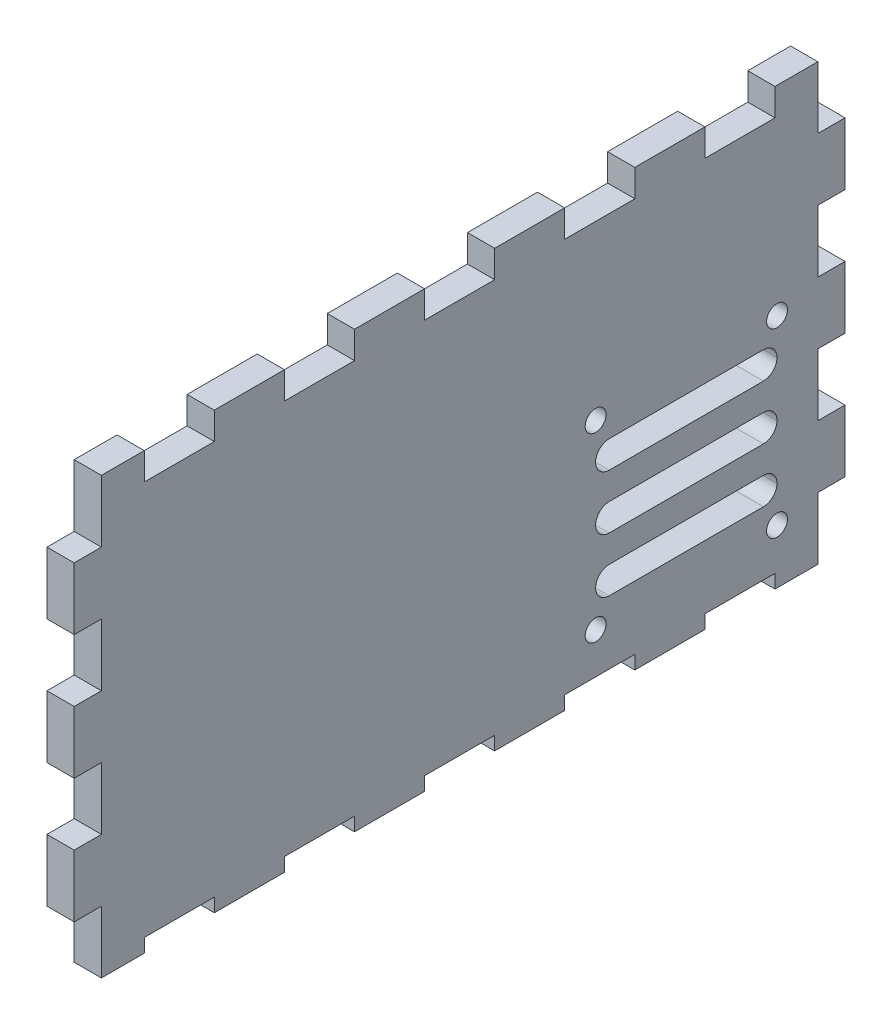
SolidWorks part; units mm, degrees
material "Balsa"
ref_plane "Front" through (0, 0, 0) normal (0, 0, 1) x (1, 0, 0)
ref_plane "Top" through (0, 0, 0) normal (0, 1, 0) x (1, 0, 0)
ref_plane "Right" through (0, 0, 0) normal (1, 0, 0) x (0, 0, -1)
sketch "Esboço1" plane through (0, 0, 0) normal (1, 0, 0) x (0, 0, -1)
  line L1 (85, -48) -> (-85, -48)
  line L2 (85, -48) -> (85, 48)
  line L3 (85, 48) -> (-85, 48)
  line L4 (-85, -48) -> (-85, 48)
  line L5 (85, -48) -> (-85, 48) construction
  line L6 (85, 48) -> (-85, -48) construction
  point P0 (0, 0)
  dimension "D1" = 170
  dimension "D2" = 96
extrude "Ressalto-extrusão1" add sketch "Esboço1" along normal blind 6
sketch "Esboço2" plane through (6, 0, 0) normal (1, 0, 0) x (0, 0, -1)
  line L0 (-7.7255, 42) -> (7.73, 42)
  line L1 (-38.6355, 42) -> (-23.18, 42)
  line L2 (-54.09, 48) -> (-69.5455, 48)
  line L3 (-23.18, 48) -> (-38.6355, 48)
  line L4 (-69.5455, 48) -> (-69.5455, 42)
  line L5 (-54.09, 48) -> (-54.09, 42)
  line L6 (23.1845, 42) -> (38.64, 42)
  line L7 (-38.6355, 48) -> (-38.6355, 42)
  line L8 (7.73, 48) -> (-7.7255, 48)
  line L9 (-23.18, 48) -> (-23.18, 42)
  line L10 (54.0945, 42) -> (69.55, 42)
  line L11 (-7.7255, 48) -> (-7.7255, 42)
  line L12 (38.64, 48) -> (23.1845, 48)
  line L13 (7.73, 48) -> (7.73, 42)
  line L14 (-54.09, -51) -> (-69.5455, -51)
  line L15 (23.1845, 48) -> (23.1845, 42)
  line L16 (-38.6355, -45) -> (-23.18, -45)
  line L17 (38.64, 48) -> (38.64, 42)
  line L18 (-7.7255, -45) -> (7.73, -45)
  line L19 (54.0945, 48) -> (54.0945, 42)
  line L20 (-23.18, -51) -> (-38.6355, -51)
  line L21 (69.55, 48) -> (69.55, 42)
  line L22 (23.1845, -45) -> (38.64, -45)
  line L23 (7.73, -51) -> (-7.7255, -51)
  line L24 (54.0945, -45) -> (69.55, -45)
  line L25 (-54.09, -45) -> (-54.09, -51)
  line L26 (38.64, -51) -> (23.1845, -51)
  line L27 (-38.6355, -45) -> (-38.6355, -51)
  line L29 (-23.18, -45) -> (-23.18, -51)
  line L31 (-7.7255, -45) -> (-7.7255, -51)
  line L33 (7.73, -45) -> (7.73, -51)
  line L35 (23.1845, -45) -> (23.1845, -51)
  line L37 (38.64, -45) -> (38.64, -51)
  line L39 (54.0945, -45) -> (54.0945, -51)
  line L41 (69.55, -45) -> (69.55, -51)
  line L47 (-69.5455, -45) -> (-69.5455, -51)
  line L48 (-69.5455, 42) -> (-54.09, 42)
  line L49 (69.55, 48) -> (54.0945, 48)
  line L50 (-69.5455, -45) -> (-54.09, -45)
  line L51 (69.55, -51) -> (54.0945, -51)
  line L53 (85.0045, 48) -> (85.0045, 42) [skipped]
  line L54 (85.0045, -45) -> (85.0045, -51) [skipped]
  dimension "D1" = 6
  dimension "D3" = 6
  dimension "D4" = 2
extrude "Corte-extrusão1" cut sketch "Esboço2" against normal up to next
sketch "Esboço3" plane through (6, 0, 0) normal (1, 0, 0) x (0, 0, -1)
  line L0 (79, -48) -> (85, -48)
  line L1 (-85, -48) -> (-79, -48)
  line L2 (-85, -48) -> (-85, -34.2857)
  line L3 (-85, -34.2857) -> (-79, -34.2857)
  line L4 (-79, -48) -> (-79, -34.2857)
  line L5 (79, -48) -> (79, -34.2857)
  line L6 (79, -34.2857) -> (85, -34.2857)
  line L7 (85, -48) -> (85, -34.2857)
  line L8 (79, -20.57) -> (85, -20.57)
  line L9 (79, -20.57) -> (79, -6.8557)
  line L10 (79, -6.8557) -> (85, -6.8557)
  line L11 (85, -20.57) -> (85, -6.8557)
  line L12 (79, 6.86) -> (85, 6.86)
  line L13 (79, 6.86) -> (79, 20.5743)
  line L14 (79, 20.5743) -> (85, 20.5743)
  line L15 (85, 6.86) -> (85, 20.5743)
  line L16 (79, 34.29) -> (85, 34.29)
  line L17 (79, 34.29) -> (79, 48.0043)
  line L18 (79, 48.0043) -> (85, 48.0043)
  line L19 (85, 34.29) -> (85, 48.0043)
  line L20 (-85, -20.57) -> (-79, -20.57)
  line L21 (-85, -20.57) -> (-85, -6.8557)
  line L22 (-85, -6.8557) -> (-79, -6.8557)
  line L23 (-79, -20.57) -> (-79, -6.8557)
  line L24 (-85, 6.86) -> (-79, 6.86)
  line L25 (-85, 6.86) -> (-85, 20.5743)
  line L26 (-85, 20.5743) -> (-79, 20.5743)
  line L27 (-79, 6.86) -> (-79, 20.5743)
  line L28 (-85, 34.29) -> (-79, 34.29)
  line L29 (-85, 34.29) -> (-85, 48.0043)
  line L30 (-85, 48.0043) -> (-79, 48.0043)
  line L31 (-79, 34.29) -> (-79, 48.0043)
  dimension "D1" = 6
  dimension "D2" = 13.7143
  dimension "D3" = 2
  dimension "D4" = 4
extrude "Corte-extrusão2" cut sketch "Esboço3" against normal up to next
sketch "Esboço4" plane through (6, 0, 0) normal (1, 0, 0) x (0, 0, -1)
  line L0 (30, -13) -> (30, -19)
  line L1 (70, -7) -> (70, -1)
  line L2 (70, -19) -> (70, -13)
  line L3 (75, -41) -> (74.9874, -41.3137)
  line L5 (30, -25) -> (30, -31)
  line L9 (79.996, -41.2008) -> (79.9834, -41.5144)
  line L11 (30, -7) -> (70, -7)
  line L12 (30, -1) -> (70, -1)
  line L13 (30, -1) -> (30, -7)
  line L14 (30, -7) -> (70, -7)
  line L15 (70, -1) -> (70, -7)
  line L17 (30, -13) -> (70, -13)
  line L19 (30, -13) -> (70, -13)
  line L20 (30, -13) -> (30, -19)
  line L21 (30, -19) -> (70, -19)
  line L22 (70, -13) -> (70, -19)
  line L23 (30, -19) -> (70, -19)
  line L24 (30, -1) -> (30, -7)
  line L25 (30, -25) -> (70, -25)
  line L27 (30, -25) -> (70, -25)
  line L28 (30, -25) -> (30, -31)
  line L29 (30, -31) -> (70, -31)
  line L30 (70, -25) -> (70, -31)
  line L32 (70, -31) -> (70, -25)
  line L37 (30, -7) -> (30, -13) [skipped]
  line L38 (70, -7) -> (70, -13) [skipped]
  line L39 (70, -19) -> (70, -25) [skipped]
  line L40 (30, -19) -> (30, -25) [skipped]
  circle A0 centre (30, 4) radius 2.3
  circle A1 centre (70, 4) radius 2.3
  circle A2 centre (30, -36) radius 2.3
  circle A3 centre (70, -36) radius 2.3
  dimension "D3" = 5
  dimension "D2" = 5
  dimension "D4" = 6
  dimension "D5" = 5
extrude "Corte-extrusão3" cut sketch "Esboço4" against normal up to next contours L12 L13 L11 L1 | L0 L21 L2 L17 | L30 L25 L5 L29 | A2 | A3 | A1 | A0 region at (6, -16, -50) region at (6, -4, -50) region at (6, -28, -50) region at (6, 4, -30) region at (6, 4, -70) region at (6, -36, -30) region at (6, -36, -70)
fillet "Filete1" radius 3 12 edges at (3, -13, -70) (3, -25, -70) (3, -13, -30) (3, -25, -30) (3, -19, -70) (3, -31, -70) (3, -31, -30) (3, -19, -30) (3, -1, -70) (3, -7, -70) (3, -7, -30) (3, -1, -30)
